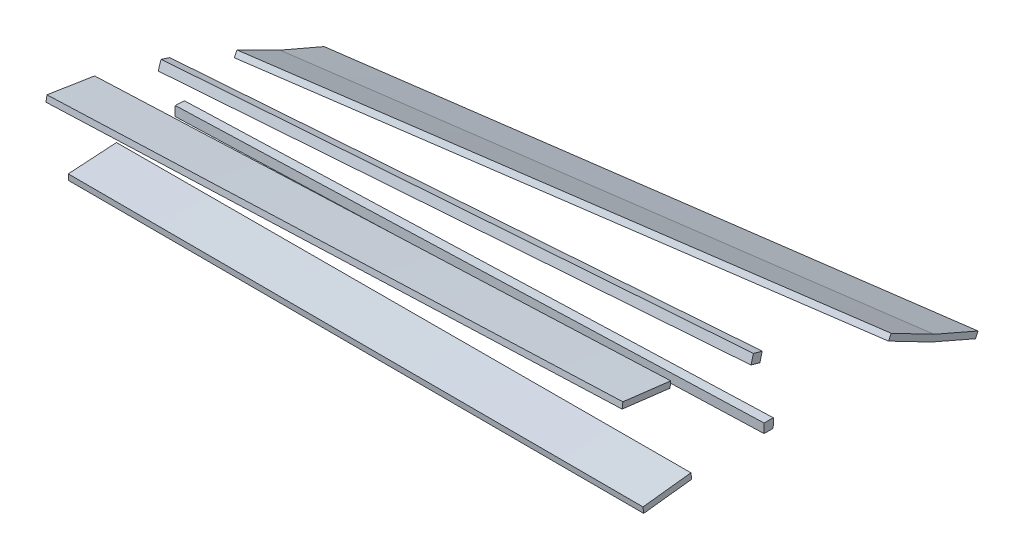
SolidWorks part; units mm, degrees
ref_plane "Front Plane" through (0, 0, 0) normal (0, 0, 1) x (1, 0, 0)
ref_plane "Top Plane" through (0, 0, 0) normal (0, 1, 0) x (1, 0, 0)
ref_plane "Right Plane" through (0, 0, 0) normal (1, 0, 0) x (0, 0, -1)
ref_plane "Plane1" through (-301.244, 0, 0) normal (1, 0, 0) x (0, 0, -1)
sketch "Sketch1" plane through (0, 0, 0) normal (1, 0, 0) x (0, 0, -1)
  line L24 (5.9245, -3.8732) -> (31.1377, -6.948)
  line L25 (31.1377, -6.948) -> (31.5221, -3.7963)
  line L26 (6.3089, -0.7215) -> (31.5221, -3.7963)
  line L27 (5.9245, -3.8732) -> (6.3089, -0.7215)
  line L28 (168.5948, -54.6475) -> (191.8825, -64.7887)
  line L29 (191.8825, -64.7887) -> (193.1501, -61.8778)
  line L30 (169.8624, -51.7366) -> (193.1501, -61.8778)
  line L31 (168.5948, -54.6475) -> (169.8624, -51.7366)
  line L32 (146.053, -42.9416) -> (168.5948, -54.6475)
  line L33 (146.053, -42.9416) -> (147.5163, -40.1239)
  line L34 (147.5163, -40.1239) -> (170.058, -51.8298)
  line L35 (168.5948, -54.6475) -> (170.058, -51.8298)
  line L36 (73.7226, -17.6893) -> (78.3761, -18.9679)
  line L37 (78.3761, -18.9679) -> (79.6548, -14.3144)
  line L38 (75.0012, -13.0358) -> (79.6548, -14.3144)
  line L39 (73.7226, -17.6893) -> (75.0012, -13.0358)
  line L40 (80.606, -52.3639) -> (85.432, -52.3698)
  line L41 (85.432, -52.3698) -> (85.4379, -47.5439)
  line L42 (80.6119, -47.5379) -> (85.4379, -47.5439)
  line L43 (80.606, -52.3639) -> (80.6119, -47.5379)
  line L44 (17.2762, -57.0653) -> (16.9093, -53.9115)
  line L45 (17.2762, -57.0653) -> (42.506, -54.1296)
  line L46 (42.506, -54.1296) -> (42.1391, -50.9759)
  line L47 (16.9093, -53.9115) -> (42.1391, -50.9759)
sketch "Sketch2" plane through (-301.244, 0, 0) normal (1, 0, 0) x (0, 0, -1)
  line L24 (29.6642, -14.5435) -> (4.5713, -10.6058)
  line L25 (4.5713, -10.6058) -> (4.079, -13.7424)
  line L26 (29.172, -17.6801) -> (4.079, -13.7424)
  line L27 (29.6642, -14.5435) -> (29.172, -17.6801)
  line L28 (149.1577, -64.4723) -> (125.8284, -54.4273)
  line L29 (149.1577, -64.4723) -> (150.4133, -61.5561)
  line L30 (150.4133, -61.5561) -> (127.084, -51.5112)
  line L31 (125.8284, -54.4273) -> (127.084, -51.5112)
  line L32 (125.8284, -54.4273) -> (103.1409, -43.0063)
  line L33 (103.1409, -43.0063) -> (104.5685, -40.1704)
  line L34 (127.256, -51.5914) -> (104.5685, -40.1704)
  line L35 (125.8284, -54.4273) -> (127.256, -51.5914)
  line L40 (41.357, -53.8117) -> (16.0067, -55.4006)
  line L41 (41.357, -53.8117) -> (41.1583, -50.6429)
  line L42 (41.1583, -50.6429) -> (15.8081, -52.2319)
  line L43 (16.0067, -55.4006) -> (15.8081, -52.2319)
  line L44 (67.6799, -30.5643) -> (63.1019, -29.037)
  line L45 (67.6799, -30.5643) -> (69.2072, -25.9864)
  line L46 (69.2072, -25.9864) -> (64.6293, -24.459)
  line L47 (63.1019, -29.037) -> (64.6293, -24.459)
  line L48 (29.6642, -14.5435) -> (4.5713, -10.6058)
  line L49 (4.5713, -10.6058) -> (4.079, -13.7424)
  line L50 (29.172, -17.6801) -> (4.079, -13.7424)
  line L51 (29.6642, -14.5435) -> (29.172, -17.6801)
  line L52 (149.1577, -64.4723) -> (125.8284, -54.4273)
  line L53 (149.1577, -64.4723) -> (150.4133, -61.5561)
  line L54 (150.4133, -61.5561) -> (127.084, -51.5112)
  line L55 (125.8284, -54.4273) -> (127.084, -51.5112)
  line L56 (125.8284, -54.4273) -> (103.1409, -43.0063)
  line L57 (103.1409, -43.0063) -> (104.5685, -40.1704)
  line L58 (127.256, -51.5914) -> (104.5685, -40.1704)
  line L59 (125.8284, -54.4273) -> (127.256, -51.5914)
  line L60 (76.6566, -54.3132) -> (71.837, -54.0655)
  line L61 (76.6566, -54.3132) -> (76.9043, -49.4936)
  line L62 (76.9043, -49.4936) -> (72.0847, -49.2458)
  line L63 (71.837, -54.0655) -> (72.0847, -49.2458)
  line L64 (41.357, -53.8117) -> (16.0067, -55.4006)
  line L65 (41.357, -53.8117) -> (41.1583, -50.6429)
  line L66 (41.1583, -50.6429) -> (15.8081, -52.2319)
  line L67 (16.0067, -55.4006) -> (15.8081, -52.2319)
  line L68 (67.6799, -30.5643) -> (63.1019, -29.037)
  line L69 (67.6799, -30.5643) -> (69.2072, -25.9864)
  line L70 (69.2072, -25.9864) -> (64.6293, -24.459)
  line L71 (63.1019, -29.037) -> (64.6293, -24.459)
  point P2 (0, 0)
  point P5 (0, 0)
  point P6 (71.4491, -49.7945)
  point P7 (76.2638, -54.2909)
loft "Loft1" add section "Sketch1" section "Sketch2" connector at (0, -3.7963, -31.5221) connector at (-301.244, -14.5435, -29.6642)
loft "Loft2" add section "Sketch1<3>" section "Sketch2<3>" connector at (0, -13.0358, -75.0012) connector at (-301.244, -24.459, -64.6293)
sketch "Sketch1<3>" plane through (0, 0, 0) normal (1, 0, 0) x (0, 0, -1) same geometry as "Sketch1"
sketch "Sketch2<3>" plane through (-301.244, 0, 0) normal (1, 0, 0) x (0, 0, -1) same geometry as "Sketch2"
loft "Loft3" add section "Sketch1<4>" section "Sketch2<4>" connector at (0, -51.8298, -170.058) connector at (-301.244, -51.5914, -127.256)
sketch "Sketch1<4>" plane through (0, 0, 0) normal (1, 0, 0) x (0, 0, -1) same geometry as "Sketch1"
sketch "Sketch2<4>" plane through (-301.244, 0, 0) normal (1, 0, 0) x (0, 0, -1) same geometry as "Sketch2"
loft "Loft4" add section "Sketch1<5>" section "Sketch2<5>" connector at (0, -61.8778, -193.1501) connector at (-301.244, -61.5561, -150.4133)
sketch "Sketch1<5>" plane through (0, 0, 0) normal (1, 0, 0) x (0, 0, -1) same geometry as "Sketch1"
sketch "Sketch2<5>" plane through (-301.244, 0, 0) normal (1, 0, 0) x (0, 0, -1) same geometry as "Sketch2"
loft "Loft5" add section "Sketch1<6>" section "Sketch2<8>" connector at (0, -47.5439, -85.4379) connector at (-301.244, -49.4936, -76.9043)
sketch "Sketch1<6>" plane through (0, 0, 0) normal (1, 0, 0) x (0, 0, -1) same geometry as "Sketch1"
sketch "Sketch2<8>" plane through (-301.244, 0, 0) normal (1, 0, 0) x (0, 0, -1) same geometry as "Sketch2"
loft "Loft6" add section "Sketch1<7>" section "Sketch2<7>" connector at (0, -50.9759, -42.1391) connector at (-301.244, -50.6429, -41.1583)
sketch "Sketch1<7>" plane through (0, 0, 0) normal (1, 0, 0) x (0, 0, -1) same geometry as "Sketch1"
sketch "Sketch2<7>" plane through (-301.244, 0, 0) normal (1, 0, 0) x (0, 0, -1) same geometry as "Sketch2"
